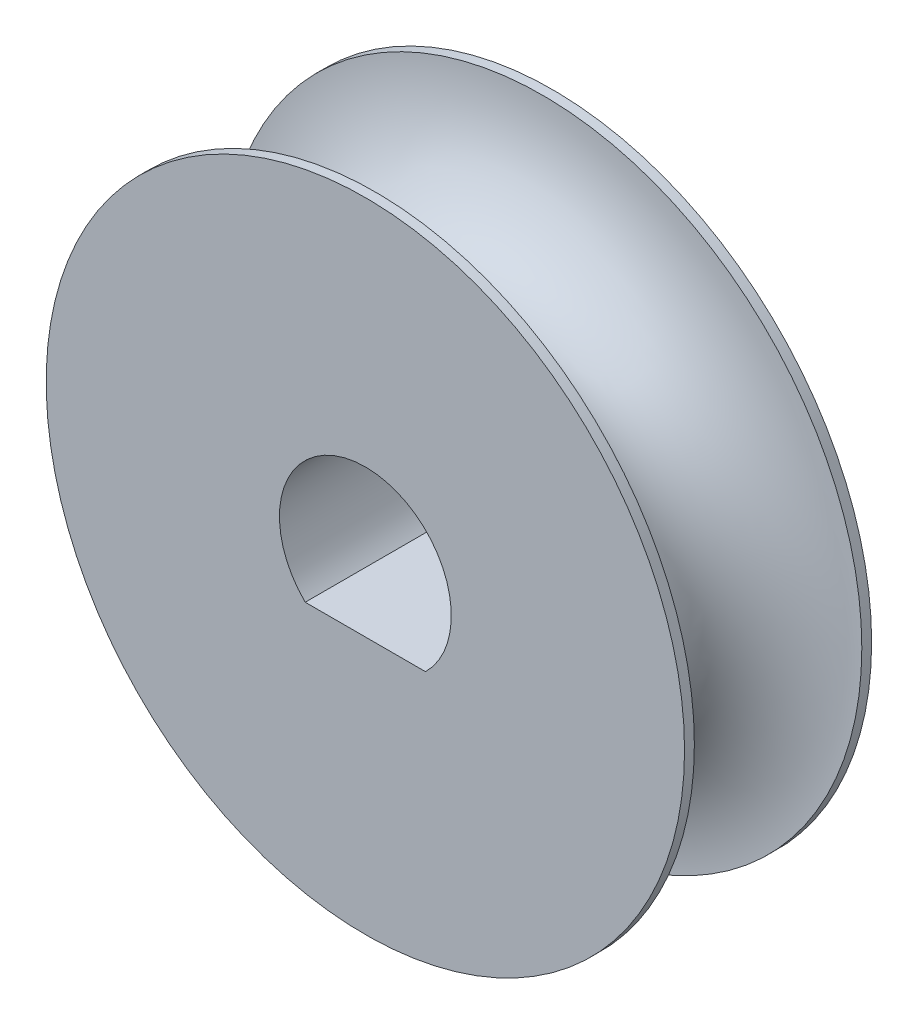
SolidWorks part; units mm, degrees
ref_plane "Front Plane" through (0, 0, 0) normal (0, 0, 1) x (1, 0, 0)
ref_plane "Top Plane" through (0, 0, 0) normal (0, 1, 0) x (1, 0, 0)
ref_plane "Right Plane" through (0, 0, 0) normal (1, 0, 0) x (0, 0, -1)
sketch "Sketch1" plane through (0, 0, 0) normal (0, 0, 1) x (1, 0, 0)
  line L0 (-24.051, 1.6575) -> (-26.5005, 1.6575)
  circle A0 centre (-25.2758, 2.9075) radius 6.5
  arc A2 (-24.051, 1.6575) -> (-26.5005, 1.6575) centre (-25.2758, 2.9075) ccw
  point P5 (-25.2758, 4.6575)
  dimension "D1" = 3.5
  dimension "D3" = 13
  dimension "D2" = 3
extrude "Boss-Extrude1" add sketch "Sketch1" against normal blind 3.81 from offset 2 contours A0 A2 region at (-31.5919, 2.9075, 0) offset against normal yes
ref_axis "Axis1" through (-25.2758, 2.9075, -5.81) along (0, 0, 1)
ref_plane "Plane1" through (-0.4531, -2.2013, 0) normal (0.2016, 0.9795, 0) x (0.9795, -0.2016, 0)
sketch "Sketch2" plane through (-0.4152, -2.2091, 0) normal (0.2016, 0.9795, 0) x (-0.9795, 0.2016, 0)
  line L0 (18.8816, -2) -> (18.8816, -5.81) construction
  line L1 (25.3816, 0.7731) -> (25.3816, -10.8262) construction
  line L2 (25.3816, -5.81) -> (25.3816, -2) construction
  line L9 (18.8816, -2) -> (18.8816, -5.81) construction
  ellipse E1 centre (18.8816, -3.905) end of major axis (16.3816, -3.905) minor radius 1.705
  point P3 (3.5525, -0.0404)
  point P4 (18.8816, -5.81)
  point P6 (18.8816, -5.61)
  point P10 (18.8816, -2)
  point P14 (21.3816, -3.905)
  dimension "D1" = 8
  dimension "D2" = 0.2
  dimension "D3" = 0.2
revolve "Cut-Revolve1" cut sketch "Sketch2" angle 360 about L1
